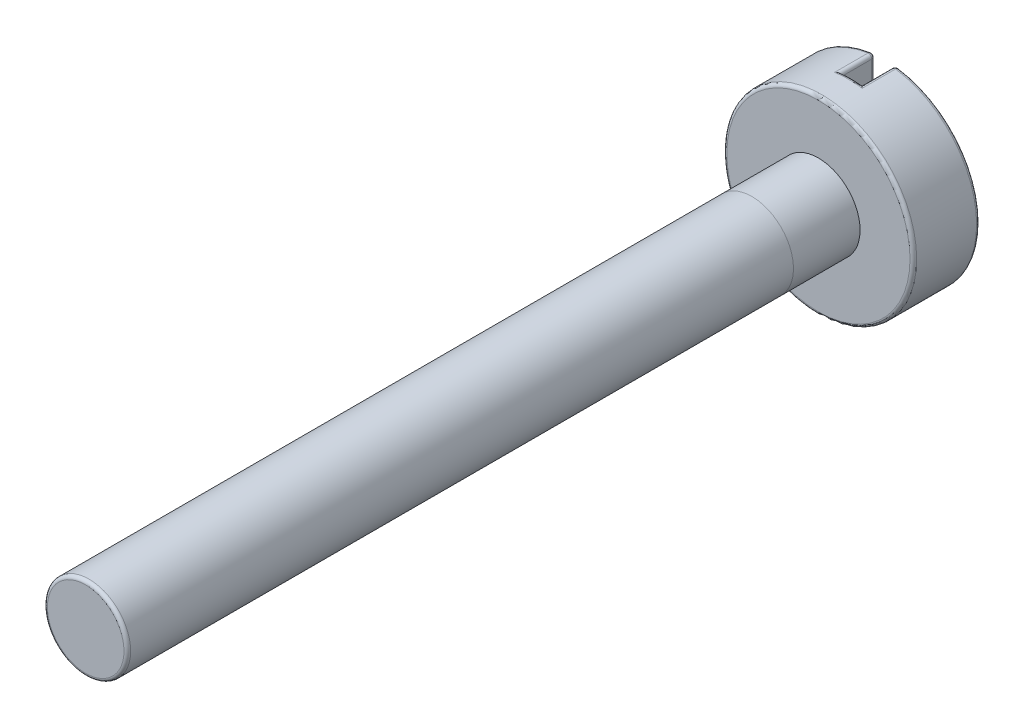
SolidWorks part; units mm, degrees
ref_plane "Front Plane" through (0, 0, 0) normal (0, 0, 1) x (1, 0, 0)
ref_plane "Top Plane" through (0, 0, 0) normal (0, 1, 0) x (1, 0, 0)
ref_plane "Right Plane" through (0, 0, 0) normal (1, 0, 0) x (0, 0, -1)
sketch "Sketch1" plane through (0, 0, 0) normal (0, 0, 1) x (1, 0, 0)
  circle A0 centre (0, 0) radius 0.625
  dimension "D1" = 1.25
extrude "Boss-Extrude1" add sketch "Sketch1" along normal blind 11 contours A0
sketch "Sketch2" plane through (0, 0, 0) normal (0, 0, 1) x (1, 0, 0)
  circle A2 centre (0, 0) radius 1.425
  circle A3 centre (0, 0) radius 1.425
  dimension "D1" = 0.8
extrude "Boss-Extrude2" add sketch "Sketch2" against normal blind 1
sketch "Sketch3" plane through (0, 0, -1) normal (0, 0, -1) x (-1, 0, 0)
  line L1 (-0.15, 4.1838) -> (0.15, 4.1838)
  line L2 (-0.15, 4.1838) -> (-0.15, -4.1838)
  line L3 (-0.15, -4.1838) -> (0.15, -4.1838)
  line L4 (0.15, 4.1838) -> (0.15, -4.1838)
  line L5 (-0.15, 4.1838) -> (0.15, -4.1838) construction
  line L6 (-0.15, -4.1838) -> (0.15, 4.1838) construction
  point P0 (0, 0)
  dimension "D1" = 0.3
extrude "Cut-Extrude1" cut sketch "Sketch3" against normal blind 0.5
fillet "Fillet1" radius 0.05 12 edges at (0.625, 0, 11) (1.425, 0, 0) (-0.15, -1.4171, -0.75) (0, -1.425, -0.5) (0.15, -1.4171, -0.75) (-0.15, 1.4171, -0.75) (0, 1.425, -0.5) (0.15, 1.4171, -0.75) (0.15, 0, -1) (1.425, 0, -1) (-1.425, 0, -1) (-0.15, 0, -1)
sketch "Sketch4" plane through (0, 0, 0) normal (0, 1, 0) x (1, 0, 0)
  line L0 (-4.2772, -1) -> (4.7645, -1)
  line L1 (-0.575, -11) -> (0.575, -11) construction
  dimension "D1" = 10
split line "Split Line1"
